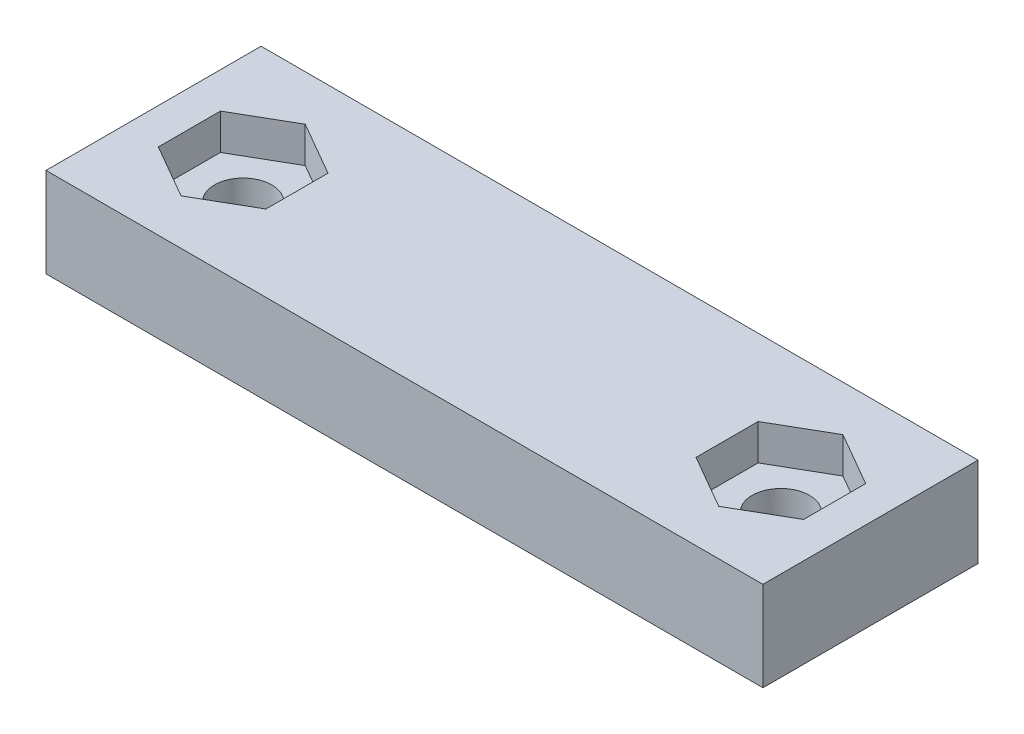
SolidWorks part; units mm, degrees
ref_plane "Front Plane" through (0, 0, 0) normal (0, 0, 1) x (1, 0, 0)
ref_plane "Top Plane" through (0, 0, 0) normal (0, 1, 0) x (1, 0, 0)
ref_plane "Right Plane" through (0, 0, 0) normal (1, 0, 0) x (0, 0, -1)
sketch "Sketch1" plane through (0, 0, 0) normal (0, 1, 0) x (1, 0, 0)
  line L1 (-20, 6) -> (20, 6)
  line L2 (-20, 6) -> (-20, -6)
  line L3 (-20, -6) -> (20, -6)
  line L4 (20, 6) -> (20, -6)
  line L5 (-20, 6) -> (20, -6) construction
  line L6 (-20, -6) -> (20, 6) construction
  point P0 (0, 0)
  dimension "D1" = 40
  dimension "D2" = 12
extrude "Boss-Extrude1" add sketch "Sketch1" along normal blind 5
sketch "Sketch2" plane through (0, 5, 0) normal (0, 1, 0) x (1, 0, 0)
  line L0 (-20, 0) -> (20, 0) construction
  line L1 (-20, 6) -> (-20, -6) construction
  line L2 (20, -6) -> (20, 6) construction
  line L3 (0, -6) -> (0, 7.5) construction
  line L4 (-20, -6) -> (20, -6) construction
  line L5 (20, 6) -> (-20, 6) construction
  circle A0 centre (15, 0) radius 1.6
  circle A1 centre (-15, 0) radius 1.6
  point P17 (0, 6)
  dimension "D1" = 3.2
  dimension "D2" = 15
extrude "Cut-Extrude2" cut sketch "Sketch2" against normal through all
sketch "Sketch3" plane through (-20, 0, 0) normal (-1, 0, 0) x (0, 0, 1)
  line L0 (-5.25, 1) -> (-5.25, 0)
  line L2 (-5.25, 0) -> (-4.25, 0)
  line L3 (-4.25, 0) -> (-4.25, 1)
  line L4 (-4.25, 1) -> (-5.25, 1)
  line L5 (-3.25, 0) -> (-2.25, 0)
  line L6 (-3.25, 1) -> (-3.25, 0)
  line L7 (-2.25, 0) -> (-2.25, 1)
  line L8 (-2.25, 1) -> (-3.25, 1)
  line L9 (-1.25, 0) -> (-0.25, 0)
  line L10 (-1.25, 1) -> (-1.25, 0)
  line L11 (-0.25, 0) -> (-0.25, 1)
  line L12 (-0.25, 1) -> (-1.25, 1)
  line L13 (0.75, 0) -> (1.75, 0)
  line L14 (0.75, 1) -> (0.75, 0)
  line L15 (1.75, 0) -> (1.75, 1)
  line L16 (1.75, 1) -> (0.75, 1)
  line L17 (2.75, 0) -> (3.75, 0)
  line L18 (2.75, 1) -> (2.75, 0)
  line L19 (3.75, 0) -> (3.75, 1)
  line L20 (3.75, 1) -> (2.75, 1)
  line L21 (4.75, 0) -> (5.75, 0)
  line L22 (4.75, 1) -> (4.75, 0)
  line L23 (5.75, 0) -> (5.75, 1)
  line L24 (5.75, 1) -> (4.75, 1)
  line L25 (6.75, 0) -> (7.75, 0)
  line L26 (6.75, 1) -> (6.75, 0)
  line L27 (7.75, 0) -> (7.75, 1)
  line L28 (7.75, 1) -> (6.75, 1)
  line L29 (8.75, 0) -> (9.75, 0)
  line L30 (8.75, 1) -> (8.75, 0)
  line L31 (9.75, 0) -> (9.75, 1)
  line L32 (9.75, 1) -> (8.75, 1)
  line L33 (-6, 5) -> (-6, 0) construction
  line L34 (-6, 0) -> (6, 0) construction
  dimension "D1" = 1
  dimension "D3" = 0.75
  dimension "D4" = 1
  dimension "D5" = 1
  dimension "D6" = 0
  dimension "D7" = 1
  dimension "D2" = 8
extrude "Teeth" cut sketch "Sketch3" against normal blind 5 and the other way blind 5 from surface starting at plane "Right Plane"
sketch "Sketch4" plane through (0, 5, 0) normal (0, 1, 0) x (1, 0, 0)
  line L0 (-15, 0) -> (-15, 3.4641) construction
  line L1 (-15, 3.4641) -> (-18, 1.7321)
  line L2 (-18, 1.7321) -> (-18, -1.7321)
  line L3 (-18, -1.7321) -> (-15, -3.4641)
  line L4 (-15, -3.4641) -> (-12, -1.7321)
  line L5 (-12, -1.7321) -> (-12, 1.7321)
  line L6 (-12, 1.7321) -> (-15, 3.4641)
  line L7 (0, 6) -> (0, -7.5) construction
  line L8 (20, 6) -> (-20, 6) construction
  line L10 (15, 0) -> (15, 3.4641) construction
  line L11 (12, 1.7321) -> (15, 3.4641)
  line L12 (12, -1.7321) -> (12, 1.7321)
  line L13 (15, -3.4641) -> (12, -1.7321)
  line L14 (18, -1.7321) -> (15, -3.4641)
  line L15 (18, 1.7321) -> (18, -1.7321)
  line L16 (15, 3.4641) -> (18, 1.7321)
  line L17 (-15, 0) -> (-15, 3.4641) construction
  circle A0 centre (-15, 0) radius 3 construction
  circle A1 centre (15, 0) radius 3 construction
  dimension "D1" = 6
extrude "Cut-Extrude4" cut sketch "Sketch4" against normal blind 2
equation "\"X-ROD-SPACING\"=45"
equation "\"Y-ROD-SPACING\"=75"
equation "\"Z-ROD-SPACING\"=17.5"
equation "\"Y-BED-OFFSET\"=2"
equation "\"Y-BED-ROD-INSET\"=3.5"
equation "\"T-SLOT-NUT-FILLET-RADIUS\"=0.25"
equation "\"T-SLOT-SCREW-SHAFT-RADIUS\"=1.75"
equation "\"T-SLOT-SCREW-SHAFT-CUTOUT-LENGTH\"=10.5"
equation "\"T-SLOT-NUT-DEPTH\"=4.2"
equation "\"T-SLOT-NUT-WIDTH\"=3"
equation "\"T-SLOT-NUT-END-DISTANCE\"=8"
equation "\"ACRYLIC-THICKNESS\"=10"
equation "\"ACRYLIC-THICKNESS2\"=4.5"
equation "\"ACRYLIC-TAB-CUTOUT-SIZE\"=\"ACRYLIC-THICKNESS\"+\"ACRYLIC-TAB-TOLERANCE\"*2"
equation "\"ACRYLIC-TAB-WIDTH\"=\"ACRYLIC-THICKNESS\""
equation "\"ACRYLIC-M3-HOLE\"=3.1"
equation "\"SMOOTHROD-CAP-SCREW-DISTANCE\"=20"
equation "\"FRAME-WIDTH-INNER\"=370"
equation "\"NEMA17-HOLE-SPACING\"=31"
equation "\"NEMA17-CENTRAL-CUTOUT\"=22.5"
equation "\"Z-BRACKET-REACH\"=55"
equation "\"TOP-BRACKET-SPACING\"=40"
equation "\"SMOOTHROD-X-LENGTH\"=350"
equation "\"SMOOTHROD-Y-LENGTH\"=350"
equation "\"SMOOTHROD-Z-LENGTH\"=350"
equation "\"SMOOTHROD-TIGHTENING-HEADROOM\"=.25"
equation "\"LEADSCREW-Z-LENGTH\"=300"
equation "\"SCREW-LENGTH-FRAME\"=\"ACRYLIC-THICKNESS\" + 10"
equation "\"SCREW-HEAD-RADIUS\"=6"
equation "\"PRINTED-X-SMOOTHROD-DIAMETER\"=8.2"
equation "\"PRINTED-X-SMOOTHROD-CUTOUT\"=10"
equation "\"PRINTED-X-BASE-HEIGHT\"=10"
equation "\"PRINTED-LM8UU-CUTOUT-SIZE\"=15.25"
equation "\"PRINTED-LM8UU-CUTOUT-LENGTH\"=24.5"
equation "\"PRINTED-X-IDLER-HEIGHT\"=16"
equation "\"PSU-MOUNTING-WIDTH\"=95"
equation "\"PSU-MOUNTING-HEIGHT\"=177"
equation "\"Y-BELT-TO-ROD-DISTANCE\"=20"
equation "\"D1@Sketch4\"=\"T-SLOT-NUT-WIDTH\"*2"
